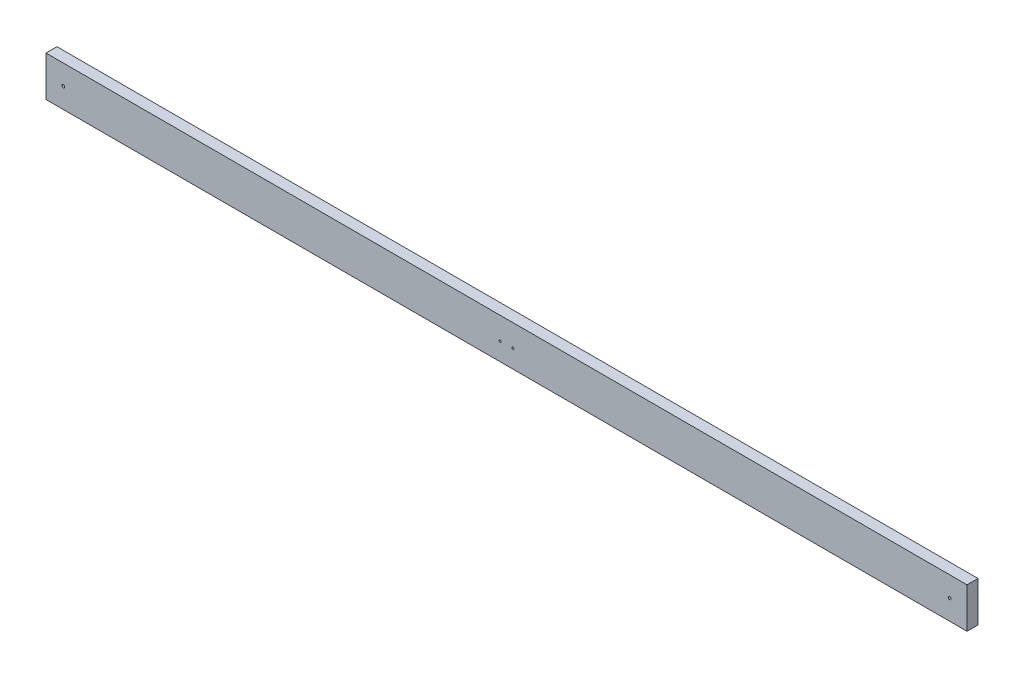
SolidWorks part; units mm, degrees
ref_plane "Front Plane" through (0, 0, 0) normal (0, 0, 1) x (1, 0, 0)
ref_plane "Top Plane" through (0, 0, 0) normal (0, 1, 0) x (1, 0, 0)
ref_plane "Right Plane" through (0, 0, 0) normal (1, 0, 0) x (0, 0, -1)
sketch "Sketch1" plane through (0, 0, 0) normal (0, 0, 1) x (1, 0, 0)
  line L1 (-1597.66, -69.85) -> (1597.66, -69.85)
  line L2 (-1597.66, -69.85) -> (-1597.66, 69.85)
  line L3 (-1597.66, 69.85) -> (1597.66, 69.85)
  line L4 (1597.66, -69.85) -> (1597.66, 69.85)
  line L5 (-1597.66, -69.85) -> (1597.66, 69.85) construction
  line L6 (-1597.66, 69.85) -> (1597.66, -69.85) construction
  point P0 (0, 0)
  dimension "D1" = 3195.32
  dimension "D2" = 139.7
extrude "Boss-Extrude1" add sketch "Sketch1" along normal blind 38.1
sketch "Sketch2" plane through (0, 0, 38.1) normal (0, 0, 1) x (1, 0, 0)
  line L1 (1597.66, 69.85) -> (-1597.66, 69.85) construction
  line L3 (-1597.66, 69.85) -> (-1597.66, -69.85) construction
  line L4 (1597.66, -69.85) -> (1597.66, 69.85) construction
  circle A0 centre (-1537.66, 0) radius 4.7625
  circle A1 centre (1537.66, 0) radius 4.7625
  dimension "D1" = 9.525
  dimension "D4" = 9.525
  dimension "D2" = 60
  dimension "D3" = 69.85
  dimension "D5" = 60
  dimension "D6" = 69.85
extrude "Cut-Extrude1" cut sketch "Sketch2" against normal through all
sketch "Sketch3" plane through (0, 0, 38.1) normal (0, 0, 1) x (1, 0, 0)
  line L0 (0, -69.85) -> (0, 69.85) construction
  line L1 (-1597.66, -69.85) -> (1597.66, -69.85) construction
  line L2 (1597.66, 69.85) -> (-1597.66, 69.85) construction
  line L3 (-28.575, -15.8242) -> (28.575, -15.8242)
  line L4 (-28.575, -15.8242) -> (-28.575, 0.0508)
  line L5 (-28.575, 0.0508) -> (28.575, 0.0508)
  line L6 (28.575, -15.8242) -> (28.575, 0.0508)
  circle A0 centre (-22.225, -7.8867) radius 3.5719
  circle A1 centre (22.225, -7.8867) radius 3.5719
  point P14 (-28.575, -7.8867)
  point P16 (0, 0.0508)
  dimension "D8" = 7.1437
  dimension "D9" = 7.1437
  dimension "D1" = 15.875
  dimension "D2" = 7.9375
  dimension "D3" = 44.45
  dimension "D4" = 6.35
  dimension "D5" = 57.15
  dimension "D6" = 77.7367
  dimension "D7" = 0
  dimension "D10" = 7.9375
extrude "Cut-Extrude2" cut sketch "Sketch3" against normal through all contours A0 | A1
